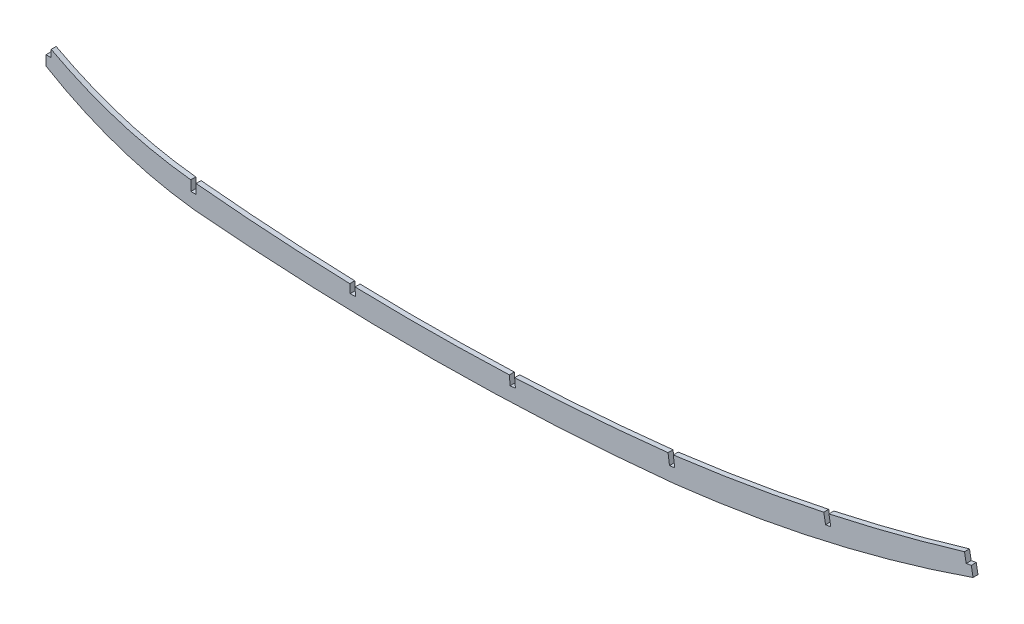
SolidWorks part; units mm, degrees
material "Balsa"
ref_plane "Front Plane" through (0, 0, 0) normal (0, 0, 1) x (1, 0, 0)
ref_plane "Top Plane" through (0, 0, 0) normal (0, 1, 0) x (1, 0, 0)
ref_plane "Right Plane" through (0, 0, 0) normal (1, 0, 0) x (0, 0, -1)
sketch "Sketch2" plane through (0, 0, 0) normal (0, 0, 1) x (1, 0, 0)
  line L0 (0, -94.4694) -> (0, -81.7694)
  line L1 (0, -94.4694) -> (93.98, -94.4694) construction
  line L2 (93.98, -126.4975) -> (93.98, -111.2575) construction
  line L3 (349.6407, -137.6462) -> (348.9613, -137.618) construction
  line L4 (349.6407, -137.6462) -> (354.8905, -137.8645) construction
  line L5 (93.98, -94.4694) -> (93.98, -126.4975) construction
  line L6 (400.2036, -124.7658) -> (400.2036, -94.4694) construction
  line L7 (590.8643, -81.3536) -> (588.5933, -68.8583)
  line L8 (0, 0) -> (672.417, 0) construction
  line L10 (93.98, -94.4694) -> (590.8643, -94.4694) construction
  line L11 (590.8643, -94.4694) -> (590.8643, -81.3536) construction
  line L12 (400.2036, -124.7658) -> (396.2207, -94.4694) construction
  arc A0 (0, -94.4694) -> (93.98, -126.4975) centre (121.7349, 108.8411) ccw
  arc A3 (93.98, -126.4975) -> (400.2036, -124.7658) centre (237.9716, 1487.1243) ccw
  arc A6 (400.2036, -124.7658) -> (590.8643, -81.3536) centre (300.4984, 753.5129) ccw
  arc A7 (93.98, -111.2575) -> (398.1841, -109.4039) centre (237.3586, 1321.3743) ccw
  arc A10 (0, -81.7694) -> (93.98, -111.2575) centre (118.1544, 130.2915) ccw
  arc A11 (398.1841, -109.4039) -> (588.5933, -68.8583) centre (254.6725, 1031.9221) ccw
  dimension "D3" = 236.9696
  dimension "D4" = 30.2963
  dimension "D5" = 400.2036
  dimension "D6" = 79.699
  dimension "D7" = 82.511
  dimension "D8" = 15.24
  dimension "D11" = 242.7557
  dimension "D14" = 1620.0336
  dimension "D15" = 883.92
  dimension "D16" = 15.494
  dimension "D18" = 1150.3133
  dimension "D1" = 12.7
  dimension "D2" = 81.7694
  dimension "D9" = 32.028
  dimension "D10" = 93.98
  dimension "D12" = 13.1158
  dimension "D13" = 496.8843
  dimension "D17" = 12.7
extrude "Boss-Extrude1" add sketch "Sketch2" against normal blind 3.175 contours A11 A7 A10 L0 A0 A3 A6 region at (5.9433, -88.1194, 0)
sketch "Sketch3" plane through (0, 0, 0) normal (0, 0, 1) x (1, 0, 0)
  line L0 (0, 0) -> (0, -81.8237) construction
  line L1 (0, 0) -> (93.98, 0) construction
  line L2 (93.98, 0) -> (93.98, -117.6075) construction
  line L4 (0, -81.8237) -> (0, -88.1813)
  line L5 (0, -88.1813) -> (3.302, -88.1813)
  line L6 (3.302, -81.8237) -> (3.302, -88.1813)
  line L8 (0, -81.8237) -> (0, -80.8493)
  line L9 (0, -80.8493) -> (3.302, -80.8493)
  line L10 (3.302, -80.8493) -> (3.302, -81.8237)
  line L12 (92.2909, -117.5313) -> (95.6691, -117.5313)
  line L13 (92.2909, -117.5313) -> (92.2909, -108.4147)
  line L14 (92.2909, -108.4147) -> (95.6691, -108.4147)
  line L15 (95.6691, -117.5313) -> (95.6691, -108.4147)
  line L30 (195.5404, -123.1566) -> (190.3839, 0) construction
  line L31 (93.98, 0) -> (612.4013, 0) construction
  line L32 (574.4157, 0) -> (588.1634, -75.3909) construction
  line L33 (193.8496, -123.1511) -> (197.2249, -123.0098)
  line L34 (193.8496, -123.1511) -> (193.5511, -116.0212)
  line L35 (197.2249, -123.0098) -> (196.9263, -115.8799)
  line L36 (193.5511, -116.0212) -> (196.9263, -115.8799)
  line L37 (397.3751, -116.2998) -> (400.7239, -115.855)
  line L38 (397.3751, -116.2998) -> (395.8625, -104.9127)
  line L39 (286.9301, 0) -> (297.4996, -122.788) construction
  line L40 (295.8233, -123.0088) -> (299.189, -122.7191)
  line L41 (295.8233, -123.0088) -> (295.1616, -115.3225)
  line L42 (299.189, -122.7191) -> (298.5274, -115.0328)
  line L43 (295.1616, -115.3225) -> (298.5274, -115.0328)
  line L44 (383.6307, 0) -> (399.0395, -116.0018) construction
  line L45 (400.7239, -115.855) -> (399.2113, -104.4679)
  line L46 (395.8625, -104.9127) -> (399.2113, -104.4679)
  line L48 (586.5153, -75.7689) -> (589.8387, -75.1629)
  line L49 (480.4996, 0) -> (498.5238, -98.843) construction
  line L50 (496.8758, -99.221) -> (500.1992, -98.615)
  line L51 (496.8758, -99.221) -> (495.4086, -91.1748)
  line L52 (500.1992, -98.615) -> (498.732, -90.5688)
  line L53 (495.4086, -91.1748) -> (498.732, -90.5688)
  line L56 (586.5153, -75.7689) -> (585.2098, -68.6095)
  line L57 (589.8387, -75.1629) -> (588.5332, -68.0035)
  line L58 (585.2098, -68.6095) -> (588.5332, -68.0035)
  point P14 (93.98, -108.4147)
  point P25 (195.2387, -115.9505)
  point P28 (297.5062, -122.864)
  point P31 (399.0495, -116.0774)
  point P39 (498.5375, -98.918)
  point P51 (588.177, -75.4659)
  dimension "D1" = 81.8237
  dimension "D2" = 6.3576
  dimension "D3" = 3.302
  dimension "D4" = 93.98
  dimension "D5" = 117.6075
  dimension "D6" = 3.3782
  dimension "D7" = 0.0762
  dimension "D8" = 92.398
  dimension "D9" = 0.0762
  dimension "D10" = 3.3782
  dimension "D11" = 190.3839
  dimension "D12" = 123.2645
  dimension "D13" = 94.92
  dimension "D14" = 96.5461
  dimension "D15" = 123.2421
  dimension "D16" = 0.0762
  dimension "D17" = 3.3782
  dimension "D18" = 96.7007
  dimension "D19" = 97.566
  dimension "D20" = 117.0207
  dimension "D21" = 0.0762
  dimension "D22" = 3.3782
  dimension "D23" = 96.8689
  dimension "D24" = 100.334
  dimension "D25" = 100.473
  dimension "D26" = 3.3782
  dimension "D27" = 0.0762
  dimension "D28" = 93.9161
  dimension "D29" = 76.6341
  dimension "D30" = 100.334
  dimension "D31" = 0.0762
  dimension "D32" = 3.3782
extrude "Cut-Extrude2" cut sketch "Sketch3" against normal through all from surface starting at face at (270.5939, -104.1002, 0)
